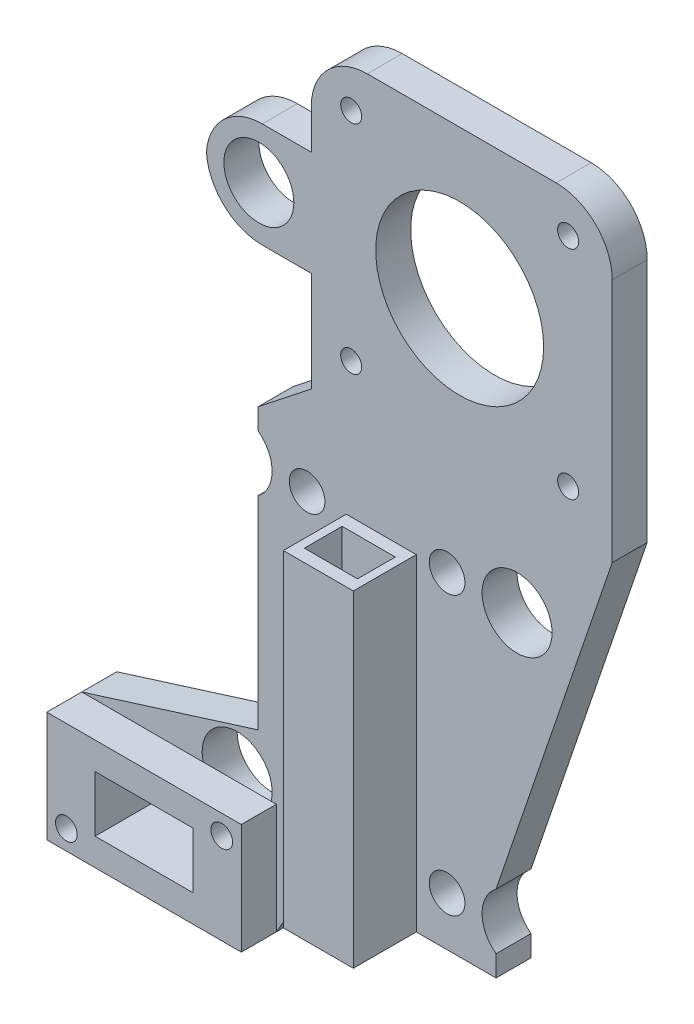
SolidWorks part; units mm, degrees
ref_plane "Front Plane" through (0, 0, 0) normal (0, 0, 1) x (1, 0, 0)
ref_plane "Top Plane" through (0, 0, 0) normal (0, 1, 0) x (1, 0, 0)
ref_plane "Right Plane" through (0, 0, 0) normal (1, 0, 0) x (0, 0, -1)
sketch "Sketch1" plane through (0, 0, 0) normal (0, 0, 1) x (1, 0, 0)
  line L0 (7, 46.7) -> (27, 46.7) construction
  line L1 (0, 0) -> (34, 0)
  line L2 (0, 0) -> (0, 3)
  line L3 (0, 53.7) -> (34, 53.7)
  line L4 (34, 0) -> (34, 3)
  line L5 (27, 46.7) -> (27, 7) construction
  line L6 (27, 7) -> (7, 7) construction
  line L7 (7, 7) -> (7, 46.7) construction
  line L8 (-3, 46.7) -> (37, 46.7) construction
  line L9 (37, 46.7) -> (37, 7) construction
  line L10 (37, 7) -> (-3, 7) construction
  line L11 (-3, 7) -> (-3, 46.7) construction
  line L12 (0, 50.7) -> (0, 53.7)
  line L13 (34, 50.7) -> (34, 53.7)
  line L14 (34, 11) -> (34, 42.7)
  line L15 (0, 11) -> (0, 42.7)
  circle A0 centre (7, 46.7) radius 2.55
  circle A1 centre (27, 46.7) radius 2.55
  circle A2 centre (7, 7) radius 2.55
  circle A3 centre (27, 7) radius 2.55
  arc A4 (0, 42.7) -> (0, 50.7) centre (-3, 46.7) ccw
  arc A5 (34, 50.7) -> (34, 42.7) centre (37, 46.7) ccw
  arc A6 (34, 11) -> (34, 3) centre (37, 7) ccw
  arc A7 (0, 3) -> (0, 11) centre (-3, 7) ccw
  dimension "D3" = 5.1
  dimension "D10" = 10
  dimension "D1" = 20
  dimension "D2" = 39.7
  dimension "D4" = 7
  dimension "D5" = 7
  dimension "D6" = 7
  dimension "D7" = 7
  dimension "D8" = 10
  dimension "D9" = 10
extrude "Boss-Extrude1" add sketch "Sketch1" along normal blind 5
sketch "Sketch2" plane through (0, 0, 5) normal (0, 0, 1) x (1, 0, 0)
  line L0 (7, 46.7) -> (27, 46.7) construction
  line L1 (12.6, 46.7) -> (22.6, 46.7)
  line L2 (12.6, 46.7) -> (12.6, 0)
  line L3 (12.6, 0) -> (22.6, 0)
  line L4 (22.6, 46.7) -> (22.6, 0)
  line L5 (7, 7) -> (27, 7) construction
  line L8 (0, 0) -> (34, 0) construction
  line L9 (0, 42.7) -> (0, 11) construction
  circle A0 centre (7, 7) radius 2.55 construction
  circle A1 centre (27, 7) radius 2.55 construction
  circle A2 centre (27, 46.7) radius 2.55 construction
  circle A3 centre (7, 46.7) radius 2.55 construction
  circle A4 centre (7, 7) radius 2.55
  circle A5 centre (27, 7) radius 2.55
  circle A6 centre (27, 46.7) radius 2.55
  circle A7 centre (7, 46.7) radius 2.55
  dimension "D1" = 10
  dimension "D2" = 12.6
extrude "Boss-Extrude2" add sketch "Sketch2" along normal blind 9 contours L4 L1 L2 L3 region at (17.6, 23.35, 5)
sketch "Sketch3" plane through (0, 0, 5) normal (0, 0, 1) x (1, 0, 0)
  line L0 (12.6, 46.7) -> (12.6, 0) construction
  line L2 (2.6, 5.8) -> (2.6, -10)
  line L3 (2.6, -10) -> (-25.2, -10)
  line L4 (-25.2, 5.8) -> (-25.2, -10)
  line L5 (-25.2, 5.8) -> (2.6, 5.8)
  line L6 (0, 0) -> (12.6, 0) construction
  circle A0 centre (7, 7) radius 4
  line M12 (0, 3) -> (0, 0)
  line M13 (0, 0) -> (12.6, 0)
  arc M23 (0, 11) -> (0, 3) centre (-3, 7) cw
  dimension "D3" = 8
  dimension "D5" = 10
  dimension "D1" = 27.8
  dimension "D2" = 15.8
  dimension "D4" = 10
extrude "Boss-Extrude3" add sketch "Sketch3" along normal blind 5 contours L5 L4 L3 L2 M13 M12 M23 | L5 L2 L3 L4 region at (-11.6533, -2.2243, 5)
sketch "Sketch5" plane through (0, 46.7, 0) normal (0, 1, 0) x (1, 0, 0)
  line L0 (12.6, -9.5) -> (22.6, -9.5) construction
  line L10 (13.8, -6.8) -> (21.4, -6.8)
  line L11 (13.8, -6.8) -> (13.8, -12.2)
  line L12 (13.8, -12.2) -> (21.4, -12.2)
  line L13 (21.4, -6.8) -> (21.4, -12.2)
  line L14 (12.6, -14) -> (12.6, -5) construction
  line L15 (22.6, -14) -> (22.6, -5) construction
  dimension "D1" = 7.6
  dimension "D2" = 5.4
  dimension "D3" = 1.2
extrude "Cut-Extrude2" cut sketch "Sketch5" against normal through all and the other way through all
sketch "Sketch6" plane through (0, 0, 5) normal (0, 0, 1) x (1, 0, 0)
  line L0 (0, 53.7) -> (0, 50.7) construction
  line L5 (7.6, 102.7) -> (50.6, 102.7)
  line L6 (7.6, 102.7) -> (7.6, 59.7)
  line L7 (7.6, 59.7) -> (50.6, 59.7)
  line L8 (50.6, 102.7) -> (50.6, 59.7)
  line L9 (7.6, 59.7) -> (0, 53.7)
  line L10 (0, 53.7) -> (34, 53.7)
  line L11 (34, 53.7) -> (50.6, 59.7)
  circle A0 centre (27, 46.7) radius 2.55 construction
  line M23 (34, 53.7) -> (0, 53.7)
  dimension "D3" = 13
  dimension "D1" = 43
  dimension "D2" = 43
  dimension "D4" = 7.6
extrude "Boss-Extrude4" add sketch "Sketch6" against normal through all contours L8 L5 L6 L7 | L11 L7 L9 M23 region at (29.1, 81.2, 5) region at (23.2857, 56.8169, 5)
sketch "Sketch8" plane through (0, 0, 5) normal (0, 0, 1) x (1, 0, 0)
  line L0 (13.3, 97) -> (44.3, 97) construction
  line L1 (44.3, 97) -> (44.3, 66) construction
  line L2 (44.3, 66) -> (13.3, 66) construction
  line L3 (13.3, 66) -> (13.3, 97) construction
  line L4 (7.6, 102.7) -> (7.6, 59.7) construction
  line L5 (7.6, 102.7) -> (50.6, 102.7) construction
  line L6 (28.8, 97) -> (28.8, 66) construction
  line L7 (13.3, 81.5) -> (44.3, 81.5) construction
  circle A0 centre (13.3, 97) radius 1.5
  circle A1 centre (44.3, 97) radius 1.5
  circle A2 centre (13.3, 66) radius 1.5
  circle A3 centre (44.3, 66) radius 1.5
  circle A4 centre (28.8, 81.5) radius 12
  point P18 (28.8, 81.5)
  dimension "D5" = 3
  dimension "D6" = 24
  dimension "D1" = 5.7
  dimension "D2" = 5.7
  dimension "D3" = 31
  dimension "D4" = 31
extrude "Cut-Extrude3" cut sketch "Sketch8" against normal through all
sketch "Sketch9" plane through (0, 0, 5) normal (0, 0, 1) x (1, 0, 0)
  line L0 (50.6, 59.7) -> (34, 11)
  circle A0 centre (37, 46.7) radius 5
  line M18 (34, 11) -> (34, 42.7)
  line M20 (34, 50.7) -> (34, 53.7)
  line M21 (34, 53.7) -> (50.6, 59.7)
  dimension "D1" = 10
extrude "Boss-Extrude5" add sketch "Sketch9" against normal up to surface (5 mm away) contours A0 L0 M18 M21 M20 region at (39.9791, 40.2387, 5) up to face at (45.8, 97, 0)
fillet "Fillet1" radius 8 2 edges at (7.6, 102.7, 2.5) (50.6, 102.7, 2.5)
sketch "Sketch11" plane through (0, 0, 5) normal (0, 0, -1) x (-1, 0, 0)
  line L0 (-2.6, -10) -> (-8.3735, 0)
  line L1 (0, 0) -> (-34, 0) construction
  line L2 (-8.3735, 0) -> (0, 0)
  line L3 (0, 0) -> (0, 3)
  line L4 (-2.6, -10) -> (25.2, -10)
  line L5 (25.2, -10) -> (25.2, 5.8)
  line L8 (-2.6, 0) -> (-2.6, -10) construction
  line L9 (25.2, 5.8) -> (0, 13.7054)
  line L10 (0, 42.7) -> (0, 11) construction
  line L11 (0, 13.7054) -> (0, 11)
  arc A1 (0, 3) -> (0, 11) centre (3, 7) ccw
  arc A2 (0, 11) -> (0, 3) centre (3, 7) ccw construction
  dimension "D2" = 5.5
  dimension "D1" = 30
extrude "Boss-Extrude7" add sketch "Sketch11" along normal up to surface (5 mm away) up to face at (42, 46.7, 0)
sketch "Sketch12" plane through (0, 0, 10) normal (0, 0, 1) x (1, 0, 0)
  line L0 (2.6, -10) -> (-25.2, -10) construction
  line L1 (-25.2, 5.8) -> (-25.2, -10) construction
  line L2 (-25.2, 5.8) -> (2.6, 5.8) construction
  line L3 (2.6, 5.8) -> (2.6, -10) construction
  circle A0 centre (-22.4, -7.2) radius 1.55
  circle A1 centre (-0.2, 3) radius 1.55
  dimension "D1" = 3.1
  dimension "D2" = 2.8
  dimension "D3" = 2.8
  dimension "D4" = 2.8
  dimension "D5" = 2.8
extrude "Cut-Extrude4" cut sketch "Sketch12" against normal up to surface (10 mm away) up to face at (13.9514, 39.8894, 0)
sketch "Sketch13" plane through (0, 0, 5) normal (0, 0, 1) x (1, 0, 0)
  line L0 (7.6, 94.7) -> (7.6, 59.7) construction
  line L1 (7.6, 74) -> (-7.4, 74)
  line L2 (7.6, 74) -> (7.6, 89)
  line L3 (7.6, 89) -> (-7.4, 89)
  line L4 (-7.4, 74) -> (-7.4, 89)
  line L5 (0.1, 89) -> (0.1, 74) construction
  line L6 (-7.4, 81.5) -> (7.6, 81.5) construction
  circle A0 centre (0.1, 81.5) radius 5
  circle A1 centre (28.8, 81.5) radius 12 construction
  circle A2 centre (28.8, 81.5) radius 12
  point P12 (0.1, 81.5)
  line M14 (7.6, 94.7) -> (7.6, 59.7)
  dimension "D3" = 10
  dimension "D1" = 15
  dimension "D2" = 15
extrude "Boss-Extrude8" add sketch "Sketch13" along direction (0, 0, 1) on the side against the normal up to surface (5 mm away) contours L4 L1 L3 A0 M14 region at (0.1, 74.2121, 5) up to face at (-20.85, -7.2, 0)
fillet "Fillet2" radius 8 2 edges at (-7.4, 74, 2.5) (-7.4, 89, 2.5)
sketch "Sketch14" plane through (0, 0, 10) normal (0, 0, 1) x (1, 0, 0)
  line L1 (-18.3, 1.9) -> (-4.3, 1.9)
  line L2 (-18.3, 1.9) -> (-18.3, -6.1)
  line L3 (-18.3, -6.1) -> (-4.3, -6.1)
  line L4 (-4.3, 1.9) -> (-4.3, -6.1)
  line L6 (-11.3, 1.9) -> (-11.3, -6.1) construction
  line L7 (-18.3, -2.1) -> (-4.3, -2.1) construction
  line L8 (-25.2, 5.8) -> (-25.2, -10) construction
  line L9 (2.6, 5.8) -> (2.6, -10) construction
  line L10 (-25.2, 5.8) -> (2.6, 5.8) construction
  line L11 (2.6, -10) -> (-25.2, -10) construction
  dimension "D1" = 14
  dimension "D2" = 8
extrude "Cut-Extrude5" cut sketch "Sketch14" against normal through all
